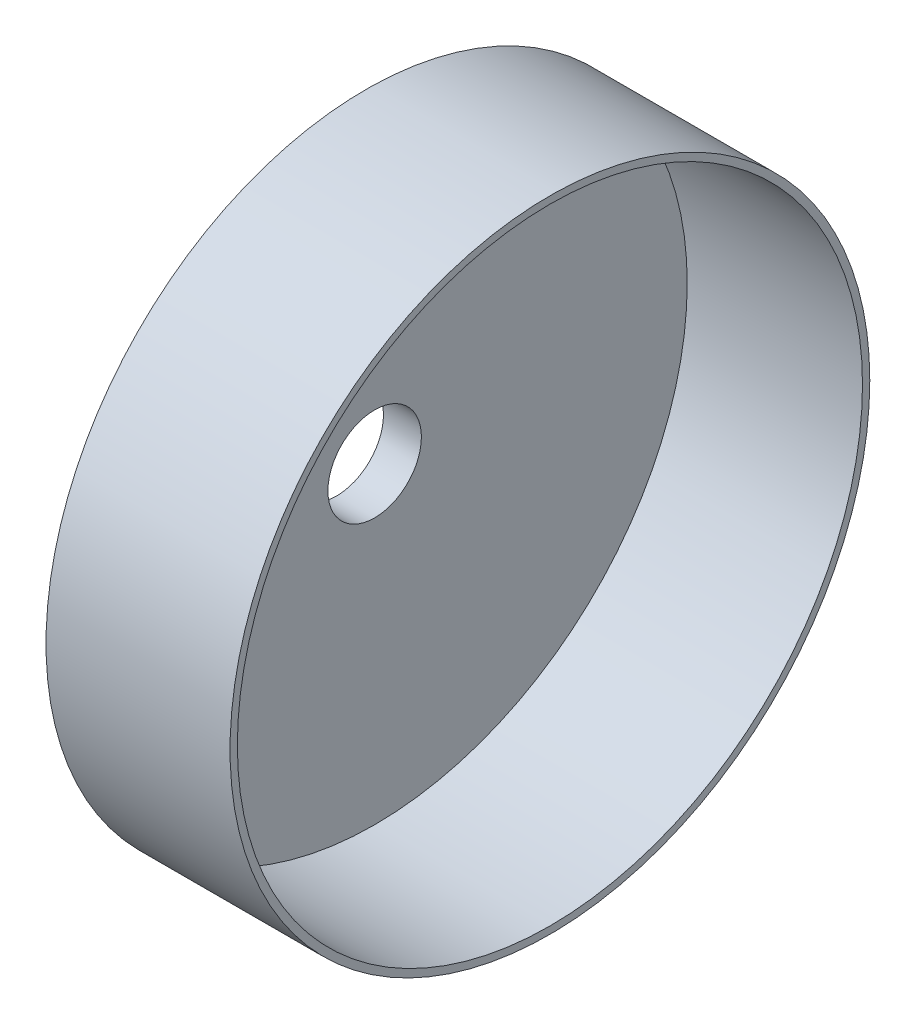
SolidWorks part; units mm, degrees
ref_plane "Front Plane" through (0, 0, 0) normal (1, 0, 0) x (0, 1, 0)
ref_plane "Top Plane" through (0, 0, 0) normal (0, 0, 1) x (0, 1, 0)
ref_plane "Right Plane" through (0, 0, 0) normal (0, 1, 0) x (-1, 0, 0)
sketch "Sketch1" plane through (0, 0, 0) normal (1, 0, 0) x (0, 1, 0)
  circle A0 centre (0, 0) radius 21.9
  dimension "D1" = 43.8
extrude "Boss-Extrude1" add sketch "Sketch1" along normal blind 0.6
sketch "Sketch2" plane through (0.6, 0, 0) normal (1, 0, 0) x (0, 1, 0)
  circle A0 centre (0, 0) radius 21.4
  circle A2 centre (0, 0) radius 21.9
  dimension "D1" = 42.8
extrude "Boss-Extrude2" add sketch "Sketch2" along normal blind 12
sketch "Sketch3" plane through (0, 0, 0) normal (-1, 0, 0) x (0, -1, 0)
  circle A0 centre (0, 0) radius 3.2
extrude "Cut-Extrude1" cut sketch "Sketch3" against normal blind 12
sketch "Sketch4" plane through (0, 0, 0) normal (-1, 0, 0) x (0, -1, 0)
  circle A0 centre (0, 0) radius 3.9
  circle A2 centre (0, 0) radius 3.2
  dimension "D1" = 7.8
extrude "Boss-Extrude3" add sketch "Sketch4" along normal blind 2
fillet "Fillet1" radius 2 1 edges at (0, 0, -3.9)
